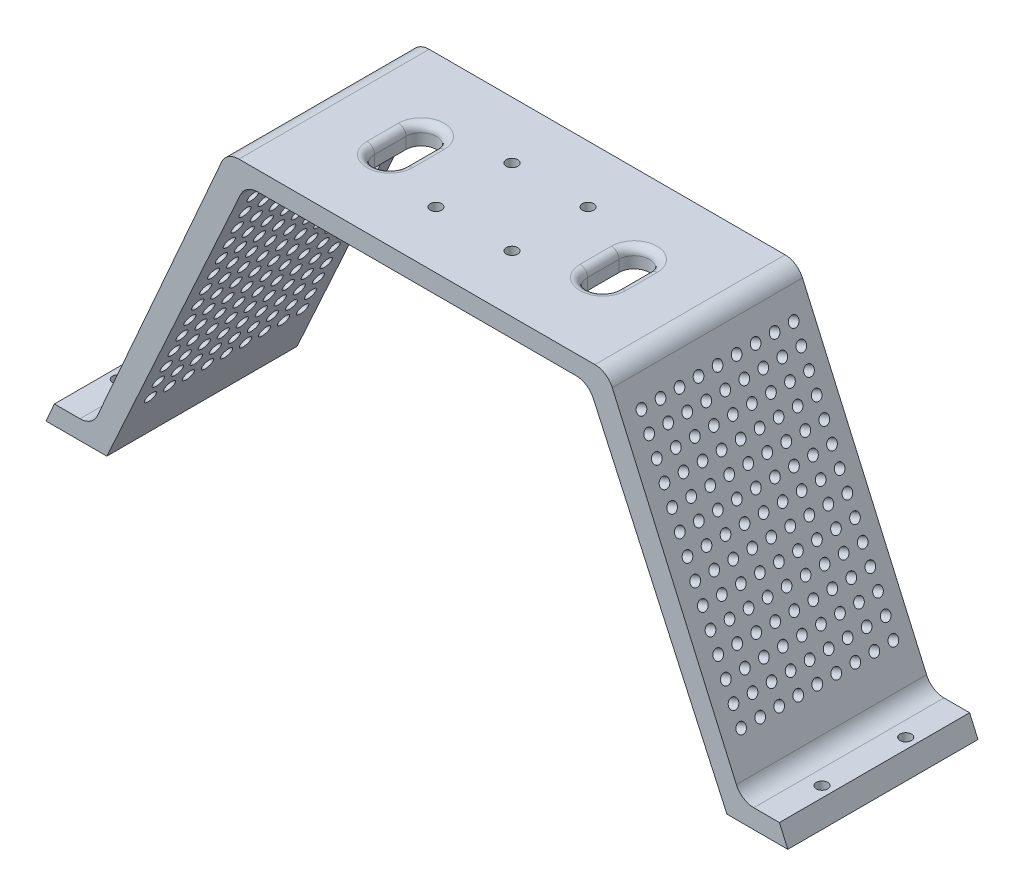
SolidWorks part; units mm, degrees
ref_plane "Front Plane" through (0, 0, 0) normal (0, 0, 1) x (1, 0, 0)
ref_plane "Top Plane" through (0, 0, 0) normal (0, 1, 0) x (1, 0, 0)
ref_plane "Right Plane" through (0, 0, 0) normal (1, 0, 0) x (0, 0, -1)
sketch "Sketch1" plane through (0, 0, 0) normal (0, 0, 1) x (1, 0, 0)
  line L0 (-87.5, 0) -> (87.5, 0)
  line L1 (-87.5, 0) -> (-50.05, 85)
  line L2 (-50.05, 85) -> (50.05, 85)
  line L3 (50.05, 85) -> (87.5, 0)
  point P4 (0, 0)
  dimension "D1" = 175
  dimension "D2" = 100.1
  dimension "D3" = 50.05
  dimension "D4" = 85
extrude "Boss-Extrude2" add sketch "Sketch1" along normal blind 50 contours L1 L2 L3 L0
sketch "Sketch3" plane through (0, 0, 50) normal (0, 0, 1) x (1, 0, 0)
  line L0 (-81.5, 0) -> (81.5, 0)
  line L1 (-87.5, 0) -> (87.5, 0) construction
  line L2 (81.5, 0) -> (45.05, 80)
  line L3 (45.05, 80) -> (-45.05, 80)
  line L4 (-45.05, 80) -> (-81.5, 0)
  line L5 (-50.05, 85) -> (50.05, 85) construction
  dimension "D1" = 163
  dimension "D2" = 6
  dimension "D3" = 90.1
  dimension "D4" = 45.05
  dimension "D5" = 5
extrude "Cut-Extrude1" cut sketch "Sketch3" against normal blind 50
fillet "Fillet1" radius 5 2 edges at (45.05, 80, 25) (-45.05, 80, 25)
sketch "Sketch5" plane through (73.2758, 32.2845, 0) normal (0.9151, 0.4032, 0) x (0, 0, -1)
  line L0 (0, 57.6053) -> (0, -35.2791) construction
  line L1 (-50, -35.2791) -> (0, -35.2791)
  line L2 (-50, -35.2791) -> (-50, -29.8151)
  line L3 (-50, -29.8151) -> (0, -29.8151)
  line L4 (0, -35.2791) -> (0, -29.8151)
  dimension "D1" = 5.464
sketch "Sketch8" plane through (0, 0, 0) normal (0, 1, 0) x (1, 0, 0)
  line L0 (93.2771, -25.8796) -> (149.3121, -25.8796)
  point P2 (0, 0)
sketch "Sketch9" plane through (0, 0, 0) normal (0, 1, 0) x (1, 0, 0)
  line L0 (-93.9767, -25.7952) -> (-133.9417, -25.7952)
sketch "Sketch10" plane through (-73.2758, 32.2845, 0) normal (-0.9151, 0.4032, 0) x (0, 0, 1)
  line L0 (0, -35.2791) -> (0, 57.6053) construction
  line L1 (50, -35.2791) -> (0, -35.2791)
  line L2 (50, -35.2791) -> (50, -29.8191)
  line L3 (50, -29.8191) -> (0, -29.8191)
  line L4 (0, -35.2791) -> (0, -29.8191)
  dimension "D1" = 5.46
extrude "Boss-Extrude4" add sketch "Sketch10" along direction (-1, 0, 0) on the side of the normal blind 10
extrude "Boss-Extrude5" add sketch "Sketch5" along direction (1, 0, 0) on the side of the normal blind 10 contours L3 L4 L1 L2
sketch "Sketch11" plane through (0, 4.9965, 0) normal (0, 1, 0) x (1, 0, 0)
  line L0 (-97.5, 0) -> (-97.5, -50) construction
  line L1 (-95.2986, -50) -> (-85.2986, -50) construction
  circle A0 centre (-92.5, -14) radius 1.5
  circle A1 centre (-92.5, -36) radius 1.5
  dimension "D1" = 22
  dimension "D2" = 5
  dimension "D3" = 14
extrude "Cut-Extrude2" cut sketch "Sketch11" against normal blind 10
sketch "Sketch12" plane through (0, 5.0002, 0) normal (0, 1, 0) x (1, 0, 0)
  line L0 (97.5, -50) -> (97.5, 0) construction
  line L1 (95.297, -50) -> (85.297, -50) construction
  circle A0 centre (92.5, -14) radius 1.5
  circle A1 centre (92.5, -36) radius 1.5
  dimension "D1" = 22
  dimension "D2" = 5
  dimension "D3" = 14
extrude "Cut-Extrude3" cut sketch "Sketch12" against normal blind 10
fillet "Fillet2" radius 5 2 edges at (85.297, 5.0002, 25) (-85.2986, 4.9965, 25)
fillet "Fillet3" radius 5 2 edges at (50.05, 85, 25) (-50.05, 85, 25)
sketch "Sketch13" plane through (0, 85, 0) normal (0, 1, 0) x (1, 0, 0)
  line L1 (-46.7892, 0) -> (-46.7892, -50) construction
  line L3 (-46.7892, 0) -> (46.7892, 0) construction
  line L4 (-46.7892, -50) -> (46.7892, -50) construction
  circle A0 centre (-9.9992, -15) radius 1.5
  circle A1 centre (10.0008, -15) radius 1.5
  circle A2 centre (-9.9992, -35) radius 1.5
  circle A3 centre (10.0008, -35) radius 1.5
  dimension "D1" = 20
  dimension "D2" = 20
  dimension "D3" = 20
  dimension "D4" = 20
  dimension "D5" = 36.79
  dimension "D6" = 15
extrude "Cut-Extrude5" cut sketch "Sketch13" against normal blind 10
sketch "Sketch14" plane through (0, 80, 0) normal (0, -1, 0) x (1, 0, 0)
  circle A0 centre (-9.9992, 35) radius 3
  circle A1 centre (-9.9992, 15) radius 3
  circle A2 centre (10.0008, 35) radius 3
  circle A3 centre (10.0008, 15) radius 3
extrude "Cut-Extrude6" cut sketch "Sketch14" against normal blind 2.5
sketch "Sketch15" plane through (0, 85, 0) normal (0, 1, 0) x (1, 0, 0)
  line L0 (-27.9992, -20.87) -> (-27.9992, -29.13) construction
  line L1 (-23.9992, -20.87) -> (-23.9992, -29.13)
  line L2 (-31.9992, -20.87) -> (-31.9992, -29.13)
  line L3 (28.0008, -20.87) -> (28.0008, -29.13) construction
  line L4 (32.0008, -20.87) -> (32.0008, -29.13)
  line L5 (24.0008, -20.87) -> (24.0008, -29.13)
  line L6 (-46.7892, 0) -> (46.7892, 0) construction
  line L7 (-46.7892, -50) -> (46.7892, -50) construction
  arc A0 (-23.9992, -20.87) -> (-31.9992, -20.87) centre (-27.9992, -20.87) ccw
  arc A1 (-31.9992, -29.13) -> (-23.9992, -29.13) centre (-27.9992, -29.13) ccw
  arc A2 (32.0008, -20.87) -> (24.0008, -20.87) centre (28.0008, -20.87) ccw
  arc A3 (24.0008, -29.13) -> (32.0008, -29.13) centre (28.0008, -29.13) ccw
  circle A4 centre (-9.9992, -15) radius 1.5 construction
  circle A5 centre (10.0008, -15) radius 1.5 construction
  point P2 (-27.9992, -25)
  point P7 (28.0008, -25)
  point P14 (28.0008, -16.87)
  dimension "D5" = 20.87
  dimension "D1" = 4
  dimension "D2" = 4
  dimension "D3" = 18
  dimension "D4" = 18
  dimension "D6" = 20.87
  dimension "D7" = 20.87
  dimension "D8" = 20.87
extrude "Cut-Extrude8" cut sketch "Sketch15" against normal blind 8.5
fillet "Fillet5" radius 2 8 edges at (-27.9992, 85, 33.13) (-23.9992, 85, 25) (-31.9992, 85, 25) (-27.9992, 85, 16.87) (28.0008, 85, 16.87) (32.0008, 85, 25) (24.0008, 85, 25) (28.0008, 85, 33.13)
sketch "Sketch16" plane through (73.2758, 32.2845, 0) normal (0.9151, 0.4032, 0) x (0, 0, -1)
  line L0 (-50, 54.3444) -> (-50, -26.5542) construction
  circle A0 centre (-45, 47.7106) radius 1.3
  dimension "D1" = 5
extrude "Cut-Extrude9" cut sketch "Sketch16" against normal blind 12
pattern_linear "LPattern1" count 9 spacing 5 along (0, 0, -1) count 14 spacing 5 along (0.4032, -0.9151, 0) of "Cut-Extrude9"
sketch "Sketch17" plane through (-73.2758, 32.2845, 0) normal (-0.9151, 0.4032, 0) x (0, 0, 1)
  line L0 (0, -26.5582) -> (0, 54.3444) construction
  line L1 (50, 54.3444) -> (0, 54.3444) construction
  circle A0 centre (5, 47.7144) radius 1.5
  dimension "D1" = 5
  dimension "D2" = 6.63
extrude "Cut-Extrude10" cut sketch "Sketch17" against normal blind 12
pattern_linear "LPattern2" count 9 spacing 5 along (0, 0, 1) count 14 spacing 5 along (-0.4032, -0.9151, 0) of "Cut-Extrude10"
